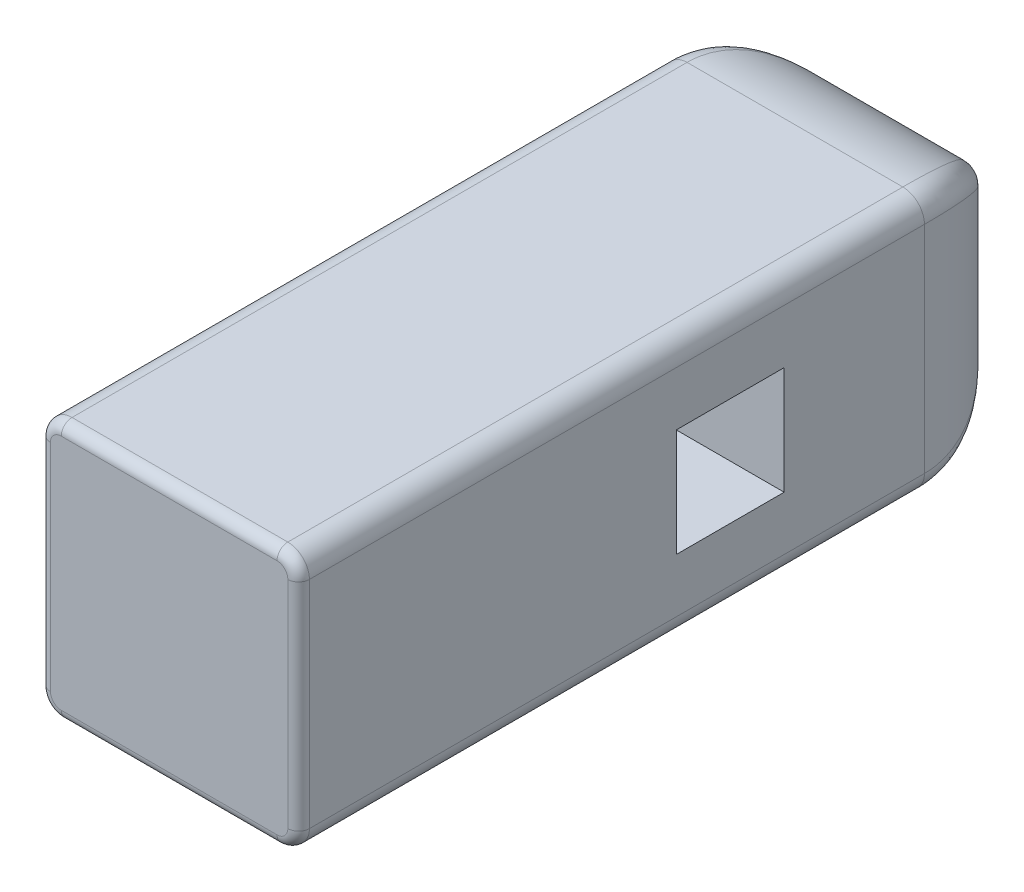
SolidWorks part; units mm, degrees
material "Acciaio al carbonio semplice"
ref_plane "Front Plane" through (0, 0, 0) normal (0, 0, 1) x (1, 0, 0)
ref_plane "Top Plane" through (0, 0, 0) normal (0, 1, 0) x (1, 0, 0)
ref_plane "Right Plane" through (0, 0, 0) normal (1, 0, 0) x (0, 0, -1)
other "Centro di massa"
sketch "Sketch1" plane through (0, 0, 0) normal (0, 0, 1) x (1, 0, 0)
  line L1 (60, 60) -> (-60, 60)
  line L2 (60, 60) -> (60, -60)
  line L3 (60, -60) -> (-60, -60)
  line L4 (-60, 60) -> (-60, -60)
  line L5 (60, 60) -> (-60, -60) construction
  line L6 (60, -60) -> (-60, 60) construction
  point P0 (0, 0)
  dimension "D1" = 120
  dimension "D2" = 120
extrude "Boss-Extrude1" add sketch "Sketch1" along normal blind 200 and the other way blind 150
sketch "Sketch3" plane through (-60, 0, 0) normal (-1, 0, 0) x (0, 0, 1)
  line L1 (25, 25) -> (-25, 25)
  line L2 (25, 25) -> (25, -25)
  line L3 (25, -25) -> (-25, -25)
  line L4 (-25, 25) -> (-25, -25)
  line L5 (25, 25) -> (-25, -25) construction
  line L6 (25, -25) -> (-25, 25) construction
  point P0 (0, 0)
  dimension "D1" = 50
  dimension "D2" = 50
extrude "Cut-Extrude2" cut sketch "Sketch3" against normal through all
fillet "Raccordo1" radius 10 4 edges at (60, -60, 25) (-60, -60, 25) (60, 60, 25) (-60, 60, 25)
fillet "Raccordo3" radius 5 8 edges at (57.0711, -57.0711, 200) (0, -60, 200) (-57.0711, -57.0711, 200) (-57.0711, 57.0711, 200) (57.0711, 57.0711, 200) (60, 0, 200) (0, 60, 200) (-60, 0, 200)
fillet "Raccordo2" radius 60 8 edges at (57.0711, -57.0711, -150) (-57.0711, -57.0711, -150) (57.0711, 57.0711, -150) (-57.0711, 57.0711, -150) (0, -60, -150) (60, 0, -150) (0, 60, -150) (-60, 0, -150)
